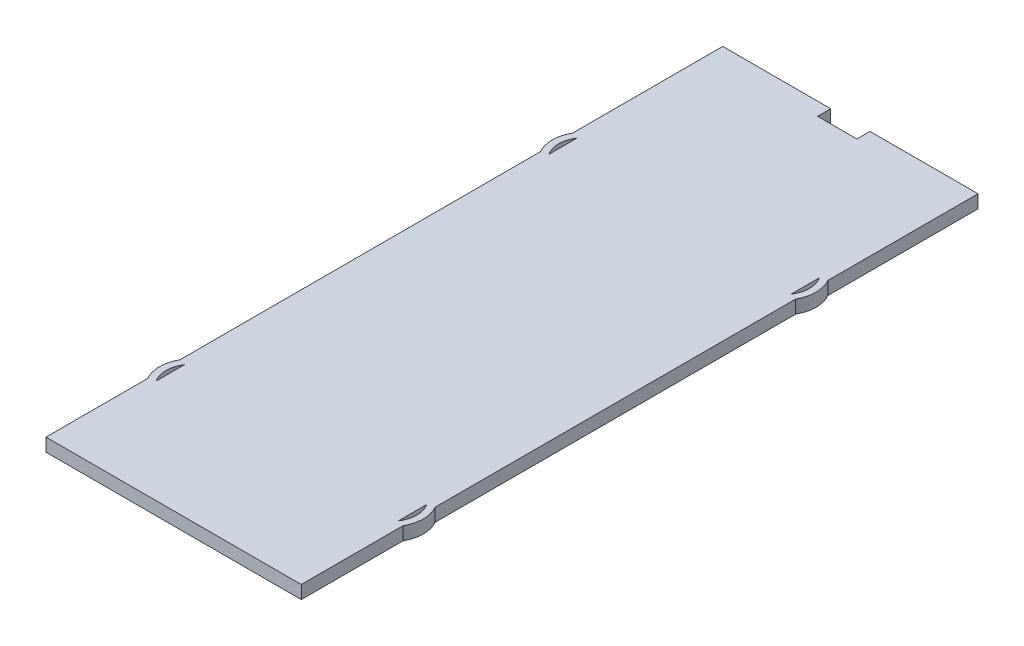
SolidWorks part; units mm, degrees
ref_plane "Front Plane" through (0, 0, 0) normal (0, 0, 1) x (1, 0, 0)
ref_plane "Top Plane" through (0, 0, 0) normal (0, 1, 0) x (1, 0, 0)
ref_plane "Right Plane" through (0, 0, 0) normal (1, 0, 0) x (0, 0, -1)
sketch "Sketch1" plane through (0, 0, 0) normal (0, 1, 0) x (1, 0, 0)
  line L1 (-15.2, 0) -> (15.2, 0) construction
  line L2 (-15.2, 0) -> (-15.2, 60) construction
  line L3 (-15.2, 60) -> (15.2, 60) construction
  line L4 (15.2, 0) -> (15.2, 60) construction
  circle A0 centre (-15.2, 60) radius 4.95
  circle A1 centre (15.2, 60) radius 4.95
  circle A2 centre (15.2, 0) radius 4.95
  circle A3 centre (-15.2, 0) radius 4.95
  point P4 (0, 0)
  dimension "D3" = 9.9
  dimension "D1" = 30.4
  dimension "D2" = 60
extrude "Boss-Extrude1" add sketch "Sketch1" along normal blind 2
sketch "Sketch2" plane through (0, 2, 0) normal (0, 1, 0) x (1, 0, 0)
  line L0 (0, 85.4) -> (0, -18) construction
  line L1 (-19.5, 85.4) -> (19.5, 85.4)
  line L2 (-19.5, 85.4) -> (-19.5, -18)
  line L3 (-19.5, -18) -> (19.5, -18)
  line L4 (19.5, 85.4) -> (19.5, -18)
  circle A0 centre (-15.2, 0) radius 4.95 construction
  circle A1 centre (-15.2, 60) radius 4.95 construction
  dimension "D1" = 18
  dimension "D2" = 25.4
  dimension "D3" = 4.3
extrude "Boss-Extrude2" add sketch "Sketch2" against normal up to surface (2 mm away) up to face at (-15.2, 0, 4.95)
sketch "Sketch3" plane through (0, 2, 0) normal (0, 1, 0) x (1, 0, 0)
  line L0 (19.5, 85.4) -> (-19.5, 85.4) construction
  line L1 (-3, 85.4) -> (3, 85.4)
  line L2 (-3, 85.4) -> (-3, 83.4)
  line L3 (-3, 83.4) -> (3, 83.4)
  line L4 (3, 85.4) -> (3, 83.4)
  point P4 (0, 85.4)
  point P7 (0, 85.4)
  dimension "D1" = 2
  dimension "D2" = 6
extrude "Cut-Extrude1" cut sketch "Sketch3" against normal through all
sketch "Sketch5" plane through (0, 0, 0) normal (0, -1, 0) x (1, 0, 0)
  line L12 (18.5, -62.1708) -> (18.5, -57.8292)
  line L13 (18.5, -2.1708) -> (18.5, 2.1708)
  line L14 (-18.5, -2.1708) -> (-18.5, 2.1708)
  line L15 (-18.5, -62.1708) -> (-18.5, -57.8292)
  line L24 (-18.5, -84.4) -> (-4, -84.4)
  line L25 (-4, -84.4) -> (-4, -82.4)
  line L26 (-4, -82.4) -> (4, -82.4)
  line L27 (4, -82.4) -> (4, -84.4)
  line L28 (4, -84.4) -> (18.5, -84.4)
  line L29 (18.5, -84.4) -> (18.5, -62.1708)
  line L30 (18.5, -57.8292) -> (18.5, -2.1708)
  line L31 (18.5, 2.1708) -> (18.5, 17)
  line L32 (18.5, 17) -> (-18.5, 17)
  line L33 (-18.5, 17) -> (-18.5, 2.1708)
  line L34 (-18.5, -2.1708) -> (-18.5, -57.8292)
  line L35 (-18.5, -62.1708) -> (-18.5, -84.4)
  arc A8 (18.5, -62.1708) -> (18.5, -57.8292) centre (15.2, -60) ccw
  arc A9 (18.5, -2.1708) -> (18.5, 2.1708) centre (15.2, 0) ccw
  arc A10 (-18.5, 2.1708) -> (-18.5, -2.1708) centre (-15.2, 0) ccw
  arc A11 (-18.5, -57.8292) -> (-18.5, -62.1708) centre (-15.2, -60) ccw
  arc A12 (18.5, -62.1708) -> (18.5, -57.8292) centre (15.2, -60) ccw
  arc A13 (18.5, -2.1708) -> (18.5, 2.1708) centre (15.2, 0) ccw
  arc A14 (-18.5, 2.1708) -> (-18.5, -2.1708) centre (-15.2, 0) ccw
  arc A15 (-18.5, -57.8292) -> (-18.5, -62.1708) centre (-15.2, -60) ccw
  dimension "D1" = 1
extrude "Cut-Extrude2" cut sketch "Sketch5" against normal through all
